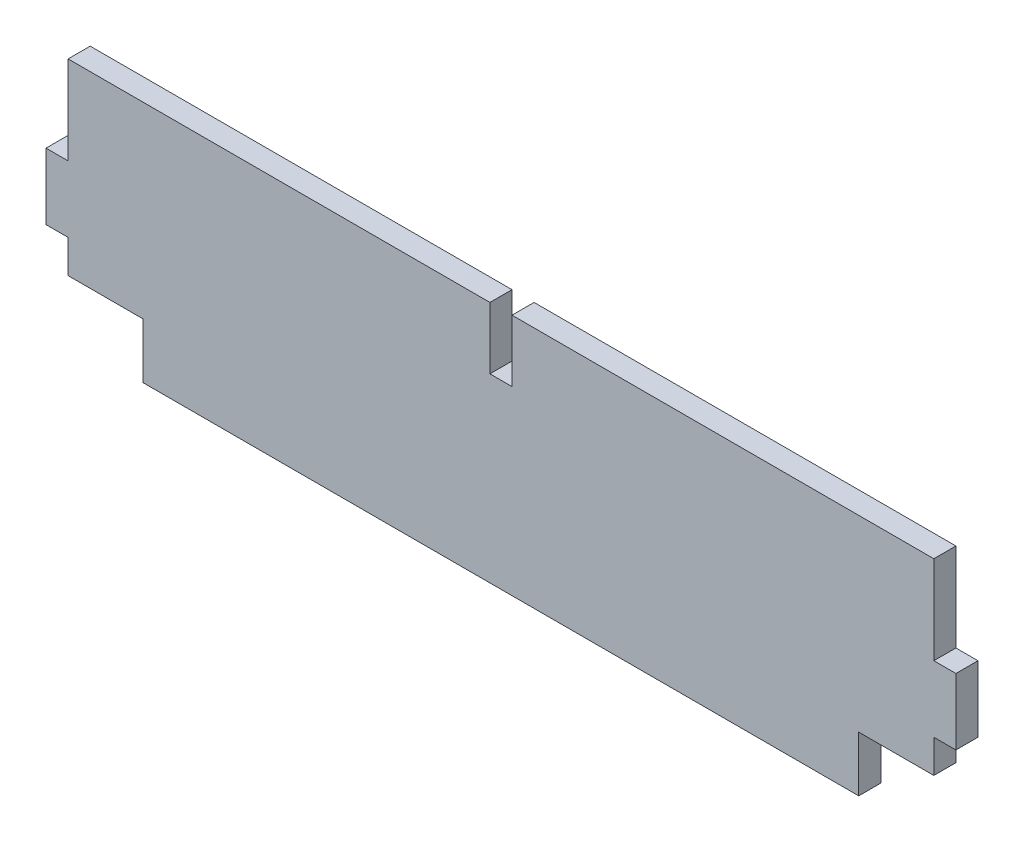
SolidWorks part; units mm, degrees
ref_plane "Plan de face" through (0, 0, 0) normal (0, 0, 1) x (1, 0, 0)
ref_plane "Plan de dessus" through (0, 0, 0) normal (0, 1, 0) x (1, 0, 0)
ref_plane "Plan de droite" through (0, 0, 0) normal (1, 0, 0) x (0, 0, -1)
sketch "Esquisse1" plane through (0, 0, 0) normal (0, 0, 1) x (1, 0, 0)
  line L0 (0, 0) -> (196, 0)
  line L1 (196, 0) -> (196, 20)
  line L2 (196, 20) -> (201, 20)
  line L3 (201, 20) -> (201, 35)
  line L4 (201, 35) -> (196, 35)
  line L5 (196, 35) -> (196, 55)
  line L7 (0, 55) -> (0, 35)
  line L8 (0, 35) -> (-5, 35)
  line L9 (-5, 35) -> (-5, 20)
  line L10 (-5, 20) -> (0, 20)
  line L11 (0, 20) -> (0, 0)
  line L12 (0, 55) -> (95.5, 55)
  line L13 (95.5, 55) -> (95.5, 41)
  line L14 (95.5, 41) -> (100.5, 41)
  line L15 (100.5, 41) -> (100.5, 55)
  line L16 (100.5, 55) -> (196, 55)
  dimension "D1" = 196
  dimension "D2" = 20
  dimension "D3" = 15
  dimension "D4" = 20
  dimension "D5" = 14
  dimension "D6" = 5
  dimension "D7" = 95.5
  dimension "D8" = 5
extrude "Boss.-Extru.1" add sketch "Esquisse1" along normal blind 5
sketch "Esquisse2" plane through (0, 0, 5) normal (0, 0, 1) x (1, 0, 0)
  line L0 (0, 12.5) -> (196, 12.5) construction
  line L1 (0, 20) -> (0, 0) construction
  line L2 (196, 0) -> (196, 20) construction
  line L3 (0, 0) -> (196, 0) construction
  line L5 (0, 0) -> (17, 0)
  line L6 (0, 0) -> (0, 12.5)
  line L7 (0, 12.5) -> (17, 12.5)
  line L8 (17, 0) -> (17, 12.5)
  line L9 (196, 0) -> (179, 0)
  line L10 (196, 0) -> (196, 12.5)
  line L11 (196, 12.5) -> (179, 12.5)
  line L12 (179, 0) -> (179, 12.5)
  dimension "D1" = 12.5
  dimension "D2" = 17
  dimension "D3" = 17
extrude "Enlèv. mat.-Extru.1" cut sketch "Esquisse2" against normal through all contours L12 L11 | L7 L8 L5 L6 region at (187.5, 6.25, 5)
